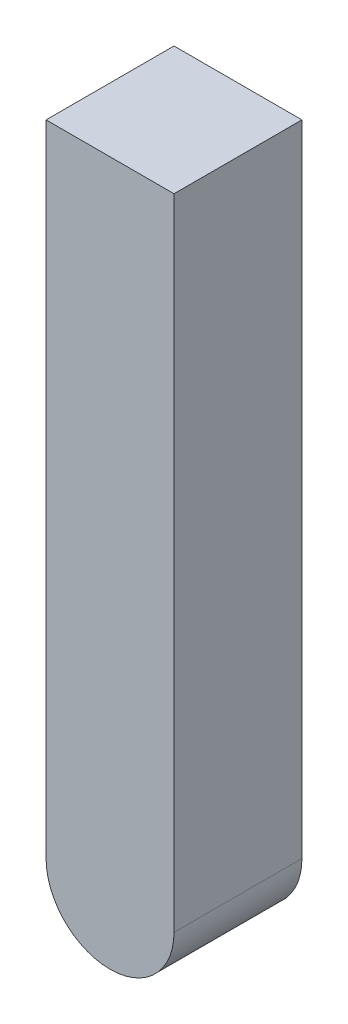
SolidWorks part; units mm, degrees
ref_plane "Plan de face" through (0, 0, 0) normal (0, 0, 1) x (1, 0, 0)
ref_plane "Plan de dessus" through (0, 0, 0) normal (0, 1, 0) x (1, 0, 0)
ref_plane "Plan de droite" through (0, 0, 0) normal (1, 0, 0) x (0, 0, -1)
sketch "Esquisse1" plane through (0, 0, 0) normal (0, 0, 1) x (1, 0, 0)
  line L1 (0, 0) -> (20, 0)
  line L2 (0, 0) -> (0, 110)
  line L3 (0, 110) -> (20, 110)
  line L4 (20, 0) -> (20, 110)
  dimension "D1" = 20
  dimension "D2" = 110
extrude "Boss.-Extru.1" add sketch "Esquisse1" along normal blind 20
sketch "Esquisse2" plane through (0, 0, 20) normal (0, 0, 1) x (1, 0, 0)
  line L0 (10, 0) -> (10, 10) construction
  line L1 (0, 0) -> (20, 0) construction
  circle A0 centre (10, 10) radius 5
  dimension "D1" = 10
  dimension "D2" = 10
extrude "Enlèv. mat.-Extru.1" [suppressed] cut sketch "Esquisse2" against normal through all both and the other way through all
fillet "Congé1" [suppressed] radius 5
fillet "Congé3" radius 10 2 edges at (0, 0, 10) (20, 0, 10)
